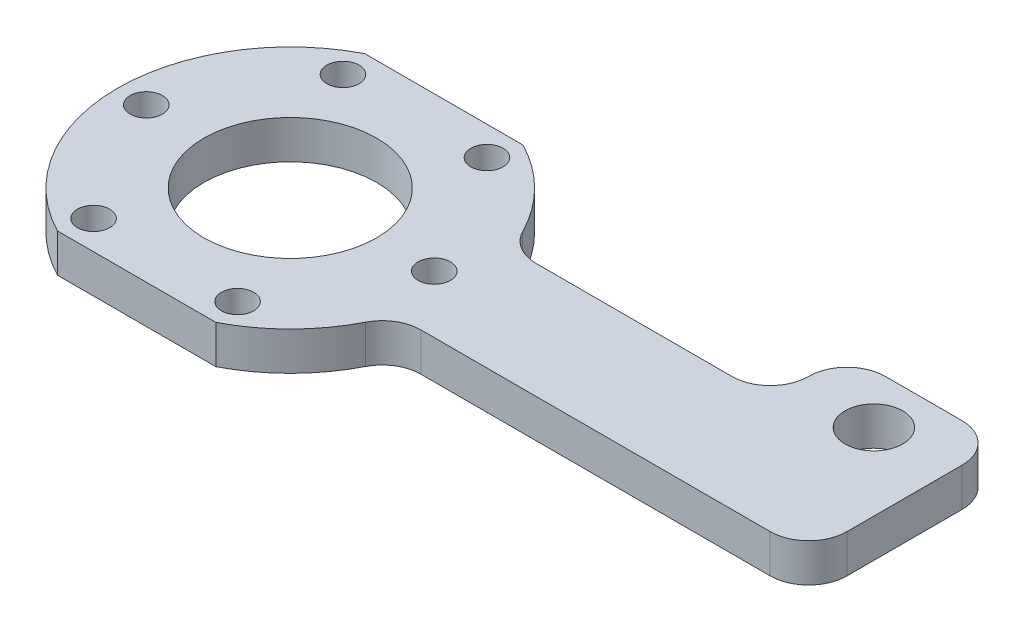
SolidWorks part; units mm, degrees
material "6063-T6"
ref_plane "Front" through (0, 0, 0) normal (0, 0, 1) x (1, 0, 0)
ref_plane "Top" through (0, 0, 0) normal (0, 1, 0) x (1, 0, 0)
ref_plane "Right" through (0, 0, 0) normal (1, 0, 0) x (0, 0, -1)
sketch "Sketch1" plane through (0, 0, 0) normal (0, 1, 0) x (1, 0, 0)
  line L0 (0, 0) -> (11.9062, 20.6222) construction
  line L2 (0, 0) -> (28.575, 0) construction
  circle A0 centre (0, 0) radius 14.2875
  circle A1 centre (0, 0) radius 28.575
  circle A2 centre (0, 0) radius 23.8125 construction
  circle A3 centre (11.9062, 20.6222) radius 2.667
  circle A9 centre (23.8125, 0) radius 2.667
  circle A10 centre (11.9063, -20.6222) radius 2.667
  circle A11 centre (-11.9062, -20.6222) radius 2.667
  circle A12 centre (-23.8125, 0) radius 2.667
  circle A13 centre (-11.9063, 20.6222) radius 2.667
  point P19 (0, 0)
  point P22 (0, 0)
  dimension "D1" = 57.15
  dimension "D2" = 28.575
  dimension "D3" = 47.625
  dimension "D4" = 5.334
  dimension "D6" = 60
extrude "Boss-Extrude1" add sketch "Sketch1" along normal blind 6.35
sketch "Sketch2" plane through (0, 0, 0) normal (0, 1, 0) x (1, 0, 0)
  line L0 (0, 0) -> (14.2875, 0) construction
  line L5 (26.9408, -9.525) -> (95.25, -9.525)
  line L7 (26.9408, 9.525) -> (95.25, 9.525)
  line L8 (95.25, -9.525) -> (95.25, 9.525)
  line L9 (14.2875, 0) -> (95.25, 0) construction
  circle A4 centre (0, 0) radius 28.575 construction
  arc A5 (26.9408, -9.525) -> (26.9408, 9.525) centre (0, 0) ccw
  dimension "D1" = 95.25
extrude "Boss-Extrude2" add sketch "Sketch2" along normal up to surface (6.35 mm away) up to face at (-23.8125, 6.35, 2.667)
sketch "Sketch3" plane through (0, 6.35, 0) normal (0, 1, 0) x (1, 0, 0)
  line L0 (0, 0) -> (82.55, 0) construction
  line L3 (95.25, 9.525) -> (69.85, 9.525)
  line L4 (95.25, 9.525) -> (95.25, 22.225)
  line L5 (95.25, 22.225) -> (69.85, 22.225)
  line L6 (69.85, 9.525) -> (69.85, 22.225)
  line L7 (95.25, 9.525) -> (69.85, 22.225) construction
  line L8 (95.25, 22.225) -> (69.85, 9.525) construction
  point P8 (82.55, 15.875)
  dimension "D2" = 22.225
  dimension "D3" = 25.4
  dimension "D1" = 82.55
extrude "Boss-Extrude3" add sketch "Sketch3" against normal up to surface (6.35 mm away) up to face at (47.2164, 0, 0)
sketch "Sketch4" plane through (0, 0, 0) normal (0, 1, 0) x (1, 0, 0)
  line L0 (0, 0) -> (82.55, 0) construction
  line L1 (82.55, 0) -> (82.55, 13.97) construction
  circle A0 centre (82.55, 13.97) radius 4.7625
  dimension "D3" = 9.525
  dimension "D1" = 82.55
  dimension "D2" = 13.97
extrude "Cut-Extrude4" cut sketch "Sketch4" along normal up to next
fillet "Fillet1" radius 6.35 6 edges at (69.85, 3.175, -9.525) (95.25, 3.175, 9.525) (69.85, 3.175, -22.225) (95.25, 3.175, -22.225) (26.9408, 3.175, 9.525) (26.9408, 3.175, -9.525)
sketch "Sketch5" plane through (0, 6.35, 0) normal (0, 1, 0) x (1, 0, 0)
  line L0 (0, 0) -> (0, 25.4) construction
  line L1 (-38.2722, 25.4) -> (47.9173, 25.4)
  line L2 (47.9173, 25.4) -> (47.9173, 36.085)
  line L3 (47.9173, 36.085) -> (-38.2722, 36.085)
  line L4 (-38.2722, 36.085) -> (-38.2722, 25.4)
  line L5 (0, 0) -> (10.6698, 0) construction
  line L6 (-38.2722, -36.085) -> (-38.2722, -25.4)
  line L7 (47.9173, -36.085) -> (-38.2722, -36.085)
  line L8 (47.9173, -25.4) -> (47.9173, -36.085)
  line L9 (-38.2722, -25.4) -> (47.9173, -25.4)
  dimension "D1" = 25.4
extrude "Cut-Extrude5" cut sketch "Sketch5" against normal through all
